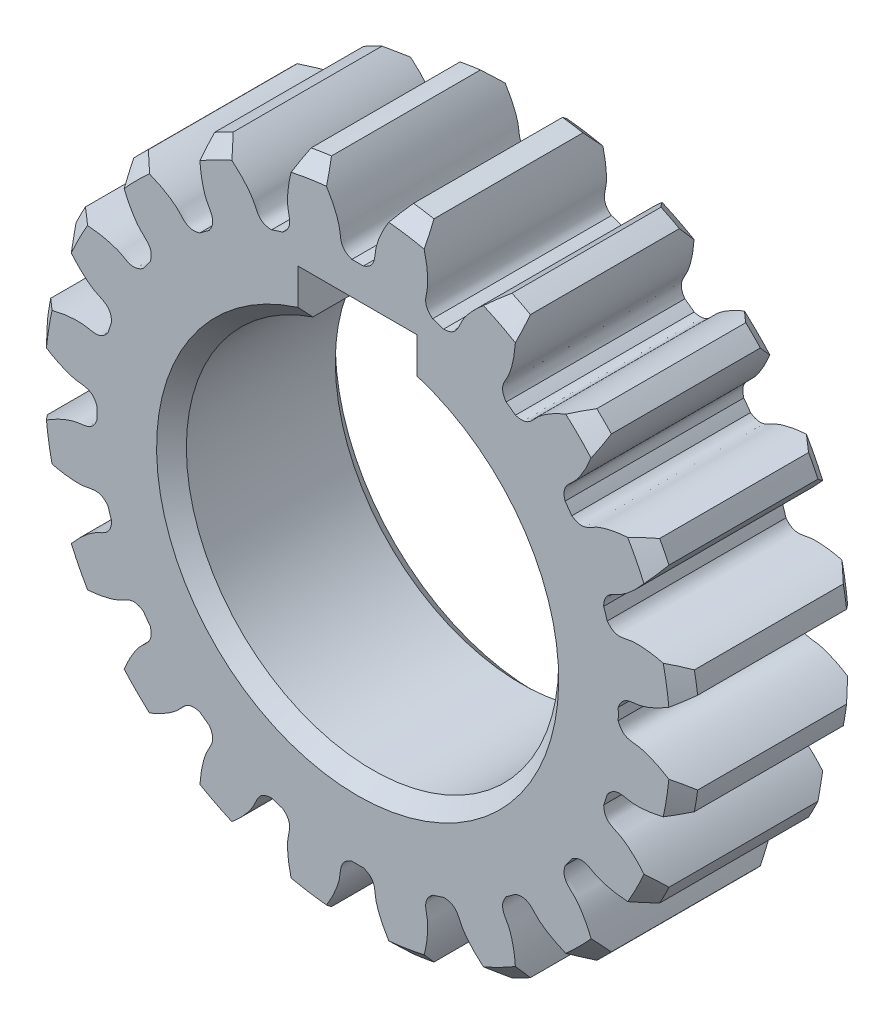
SolidWorks part; units mm, degrees
ref_plane "前视基准面" through (0, 0, 0) normal (0, 0, 1) x (1, 0, 0)
ref_plane "上视基准面" through (0, 0, 0) normal (0, 1, 0) x (1, 0, 0)
ref_plane "右视基准面" through (0, 0, 0) normal (1, 0, 0) x (0, 0, -1)
sketch "草图1" plane through (0, 0, 0) normal (0, 0, 1) x (1, 0, 0)
  circle A0 centre (0, 0) radius 22
extrude "凸台-拉伸1" add sketch "草图1" along normal blind 12
ref_axis "基准轴1" through (0, 0, -0.6) along (0, 0, 1)
chamfer "倒角1" distance 1 angle 45 2 edges at (22, 0, 0) (22, 0, 12)
sketch "草图2" plane through (0, 0, 0) normal (0, 0, 1) x (1, 0, 0)
  line L0 (0, 0) -> (0, 22) construction
  circle A0 centre (0, 0) radius 22 construction
  arc A1 (0.3866, 17.4957) -> (-0.3866, 17.4957) centre (0, 0) ccw
  arc A2 (6.3623, 24.9965) -> (-6.3623, 24.9965) centre (0, 0) ccw
  spline S0 degree 3 poles (0.3866, 17.4957) (1.2224, 17.787) (1.1142, 18.3742) (1.2258, 18.94) (1.2378, 18.9951) (1.2526, 19.0573) (1.2706, 19.1264) (1.292, 19.2024) (1.317, 19.2851) (1.3461, 19.3745) (1.3793, 19.4704) (1.4171, 19.5726) (1.4597, 19.6811) (1.5073, 19.7956) (1.5603, 19.9161) (1.6187, 20.0423) (1.683, 20.174) (1.7534, 20.3112) (1.83, 20.4535) (1.9132, 20.6008) (2.0031, 20.7529) (2.1, 20.9095) (2.204, 21.0705) (2.3155, 21.2356) (2.4346, 21.4046) (2.5615, 21.5772) (2.6964, 21.7533) (2.8395, 21.9324) (2.991, 22.1145) (3.1509, 22.2992) (3.3196, 22.4862) (3.4971, 22.6753) (3.6837, 22.8662) (3.8793, 23.0586) (4.0843, 23.2521) (4.2986, 23.4467) (4.5225, 23.6418) (4.7559, 23.8372) (4.9991, 24.0327) (5.2521, 24.2278) (5.515, 24.4223) (5.8829, 24.6833) (6.1679, 24.8727) (6.3623, 24.9965) knots 0 0 0 0 0.165916 0.170906 0.176664 0.183189 0.190482 0.198542 0.207371 0.216967 0.22733 0.238462 0.250361 0.263027 0.276462 0.290664 0.305634 0.321371 0.337876 0.355149 0.37319 0.391998 0.411574 0.431917 0.453028 0.474907 0.497554 0.520968 0.54515 0.570099 0.595817 0.622302 0.649554 0.677575 0.706363 0.735918 0.766242 0.797333 0.829191 0.861818 0.895212 0.929373 1 1 1 1
  spline S1 degree 3 poles (-0.3866, 17.4957) (-1.2224, 17.787) (-1.1142, 18.3742) (-1.2258, 18.94) (-1.2378, 18.9951) (-1.2526, 19.0573) (-1.2706, 19.1264) (-1.292, 19.2024) (-1.317, 19.2851) (-1.3461, 19.3745) (-1.3793, 19.4704) (-1.4171, 19.5726) (-1.4597, 19.6811) (-1.5073, 19.7956) (-1.5603, 19.9161) (-1.6187, 20.0423) (-1.683, 20.174) (-1.7534, 20.3112) (-1.83, 20.4535) (-1.9132, 20.6008) (-2.0031, 20.7529) (-2.1, 20.9095) (-2.204, 21.0705) (-2.3155, 21.2356) (-2.4346, 21.4046) (-2.5615, 21.5772) (-2.6964, 21.7533) (-2.8395, 21.9324) (-2.991, 22.1145) (-3.1509, 22.2992) (-3.3196, 22.4862) (-3.4971, 22.6753) (-3.6837, 22.8662) (-3.8793, 23.0586) (-4.0843, 23.2521) (-4.2986, 23.4467) (-4.5225, 23.6418) (-4.7559, 23.8372) (-4.9991, 24.0327) (-5.2521, 24.2278) (-5.515, 24.4223) (-5.8829, 24.6833) (-6.1679, 24.8727) (-6.3623, 24.9965) knots 0 0 0 0 0.165916 0.170906 0.176664 0.183189 0.190482 0.198542 0.207371 0.216967 0.22733 0.238462 0.250361 0.263027 0.276462 0.290664 0.305634 0.321371 0.337876 0.355149 0.37319 0.391998 0.411574 0.431917 0.453028 0.474907 0.497554 0.520968 0.54515 0.570099 0.595817 0.622302 0.649554 0.677575 0.706363 0.735918 0.766242 0.797333 0.829191 0.861818 0.895212 0.929373 1 1 1 1
extrude "切除-拉伸1" cut sketch "草图2" along normal through all
pattern_circular "阵列(圆周)1" count 20 every 18 about axis through (0, 0, -0.6) along (0, 0, 1) of "切除-拉伸1"
sketch "草图4" plane through (0, 0, 0) normal (0, 0, 1) x (1, 0, 0)
  line L0 (-4, 15.3) -> (4, 15.3)
  line L1 (-4, 15.3) -> (-4, 11.8427)
  line L2 (4, 15.3) -> (4, 11.8427)
  arc A0 (-4, 11.8427) -> (4, 11.8427) centre (0, 0) ccw
extrude "切除-拉伸2" cut sketch "草图4" along normal through all
chamfer "倒角2" distance 1 angle 45 1 edges at (0, -12.5, 12)
chamfer "倒角3" distance 1 angle 45 1 edges at (0, -12.5, 0)
sketch "草图5" plane through (0, 0, 12) normal (0, 0, 1) x (1, 0, 0)
  circle A0 centre (0, 0) radius 20
sketch "草图6" plane through (0, 0, 0) normal (0, 0, -1) x (-1, 0, 0)
  circle A0 centre (0, 0) radius 20
